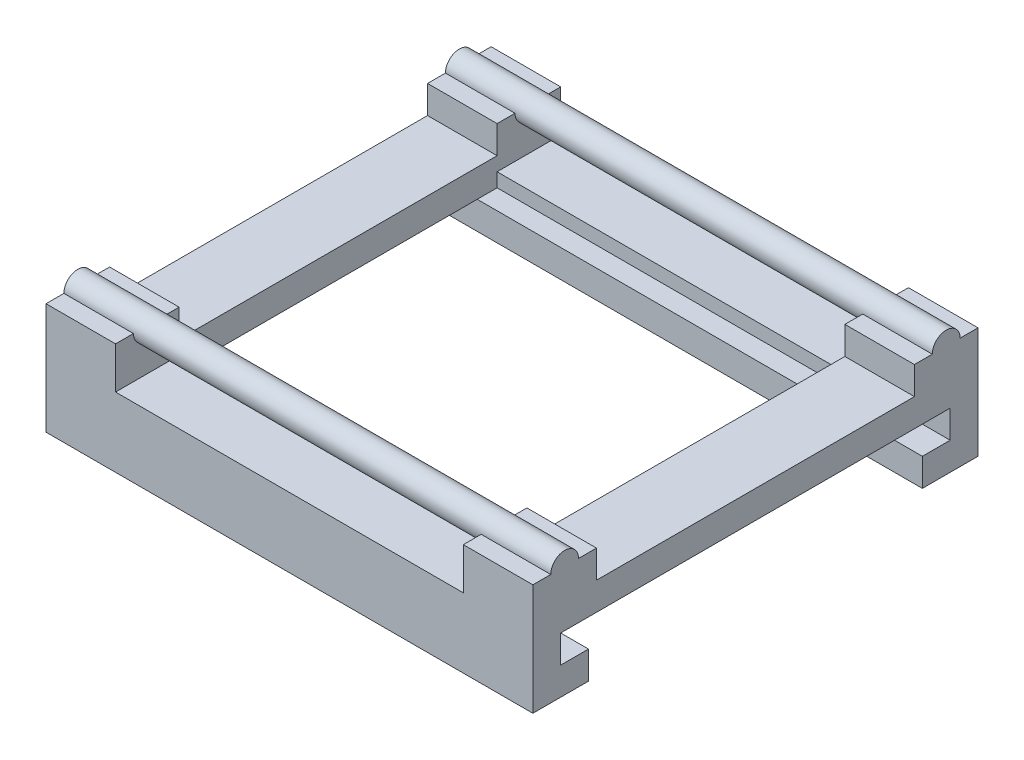
SolidWorks part; units mm, degrees
ref_plane "前视基准面" through (0, 0, 0) normal (0, 0, 1) x (1, 0, 0)
ref_plane "上视基准面" through (0, 0, 0) normal (0, 1, 0) x (1, 0, 0)
ref_plane "右视基准面" through (0, 0, 0) normal (1, 0, 0) x (0, 0, -1)
sketch "草图1" plane through (0, 0, 0) normal (0, 1, 0) x (1, 0, 0)
  line L8 (-25.1699, 20.3665) -> (9.8301, -11.6335)
  line L9 (-25.1699, 20.3665) -> (9.8301, 20.3665)
  line L10 (-25.1699, 20.3665) -> (-25.1699, -11.6335)
  line L11 (-25.1699, -11.6335) -> (9.8301, -11.6335)
  line L12 (9.8301, 20.3665) -> (9.8301, -11.6335)
  line L13 (-25.1699, -11.6335) -> (9.8301, 20.3665)
  line L15 (-20.1699, -7.0621) -> (4.8301, -7.0621)
  line L16 (-20.1699, -7.0621) -> (-20.1699, 15.7951)
  line L17 (-20.1699, 15.7951) -> (4.8301, 15.7951)
  line L18 (4.8301, -7.0621) -> (4.8301, 15.7951)
  line L19 (-20.1699, -7.0621) -> (4.8301, 15.7951) construction
  line L20 (-20.1699, 15.7951) -> (4.8301, -7.0621) construction
  point P4 (-7.6699, 4.3665)
  dimension "D1" = 32
  dimension "D2" = 35
  dimension "D3" = 25
extrude "凸台-拉伸1" add sketch "草图1" along normal blind 2 contours L13 L16 L8 L10 | L10 L9 L12 L11 region at (-22.8088, 0, -4.3665)
extrude "切除-拉伸2" cut sketch "草图1<3>" along normal blind 2 contours L16 L13 L8 | L17 L8 L13 | L8 L18 L13 | L13 L15 L8 region at (-7.6699, 0, -11.9856) region at (-16.0032, 0, -4.3665) region at (0.6634, 0, -4.3665) region at (-7.6699, 0, 3.2525)
sketch "草图1<3>" plane through (0, 0, 0) normal (0, 1, 0) x (1, 0, 0) same geometry as "草图1"
sketch "草图3" plane through (0, 0, 0) normal (0, -1, 0) x (1, 0, 0)
  line L0 (9.8301, -20.3665) -> (9.8301, 11.6335) construction
  line L1 (-25.1699, -20.3665) -> (9.8301, -20.3665)
  line L2 (-25.1699, -20.3665) -> (-25.1699, -16.3665)
  line L3 (-25.1699, -16.3665) -> (9.8301, -16.3665)
  line L4 (9.8301, -20.3665) -> (9.8301, -16.3665)
  line L6 (-25.1699, 11.6335) -> (9.8301, 11.6335)
  line L7 (-25.1699, 11.6335) -> (-25.1699, 7.6335)
  line L8 (-25.1699, 7.6335) -> (9.8301, 7.6335)
  line L9 (9.8301, 11.6335) -> (9.8301, 7.6335)
  dimension "D1" = 4
  dimension "D2" = 4
extrude "凸台-拉伸2" add sketch "草图3" along normal blind 4
sketch "草图4" plane through (0, 0, 7.6335) normal (0, 0, -1) x (-1, 0, 0)
  line L0 (25.1699, -4) -> (25.1699, 0) construction
  line L1 (-9.8301, 0) -> (25.1699, 0)
  line L2 (-9.8301, 0) -> (-9.8301, -2)
  line L3 (-9.8301, -2) -> (25.1699, -2)
  line L4 (25.1699, 0) -> (25.1699, -2)
  dimension "D1" = 2
extrude "切除-拉伸3" cut sketch "草图4" against normal blind 2
sketch "草图5" plane through (0, 0, -16.3665) normal (0, 0, 1) x (1, 0, 0)
  line L0 (-25.1699, -4) -> (-25.1699, 0) construction
  line L1 (9.8301, 0) -> (-25.1699, 0)
  line L2 (9.8301, 0) -> (9.8301, -2)
  line L3 (9.8301, -2) -> (-25.1699, -2)
  line L4 (-25.1699, 0) -> (-25.1699, -2)
extrude "切除-拉伸4" cut sketch "草图5" against normal blind 2
sketch "草图6" plane through (0, 2, 0) normal (0, 1, 0) x (1, 0, 0)
  line L1 (9.8301, -11.6335) -> (4.8301, -11.6335)
  line L2 (9.8301, -11.6335) -> (9.8301, -7.0621)
  line L3 (9.8301, -7.0621) -> (4.8301, -7.0621)
  line L4 (4.8301, -11.6335) -> (4.8301, -7.0621)
  line L5 (-25.1699, -11.6335) -> (-20.1699, -11.6335)
  line L6 (-25.1699, -11.6335) -> (-25.1699, -7.0621)
  line L7 (-25.1699, -7.0621) -> (-20.1699, -7.0621)
  line L8 (-20.1699, -11.6335) -> (-20.1699, -7.0621)
  line L9 (-25.1699, 20.3665) -> (-20.1699, 20.3665)
  line L10 (-25.1699, 20.3665) -> (-25.1699, 15.7951)
  line L11 (-25.1699, 15.7951) -> (-20.1699, 15.7951)
  line L12 (-20.1699, 20.3665) -> (-20.1699, 15.7951)
  line L13 (9.8301, 20.3665) -> (4.8301, 20.3665)
  line L14 (9.8301, 20.3665) -> (9.8301, 15.7951)
  line L15 (9.8301, 15.7951) -> (4.8301, 15.7951)
  line L16 (4.8301, 20.3665) -> (4.8301, 15.7951)
  line M19 (9.8301, -11.6335) -> (9.8301, 20.3665)
  line M20 (9.8301, 20.3665) -> (-25.1699, 20.3665)
extrude "凸台-拉伸3" add sketch "草图6" along normal blind 2 contours L16 L15 M20 M19 | L2 L1 L4 L3 | L6 L5 L8 L7 | L10 L9 L12 L11 region at (7.3301, 2, -18.0808)
sketch "草图7" plane through (0, 2, 0) normal (0, 1, 0) x (1, 0, 0)
  line L1 (-20.1699, -11.6335) -> (4.8301, -11.6335)
  line L2 (-20.1699, -11.6335) -> (-20.1699, -7.0621)
  line L3 (-20.1699, -7.0621) -> (4.8301, -7.0621)
  line L4 (4.8301, -11.6335) -> (4.8301, -7.0621)
  line L6 (4.8301, 15.7951) -> (-20.1699, 15.7951)
  line L7 (4.8301, 15.7951) -> (4.8301, 20.3665)
  line L8 (4.8301, 20.3665) -> (-20.1699, 20.3665)
  line L9 (-20.1699, 15.7951) -> (-20.1699, 20.3665)
extrude "切除-拉伸5" cut sketch "草图7" against normal blind 1
sketch "草图9" plane through (-20.1699, 0, 0) normal (1, 0, 0) x (0, 0, -1)
  line L0 (20.3665, 4) -> (15.7951, 4) construction
  line L1 (-11.6335, 4) -> (-7.0621, 4) construction
  circle A0 centre (18.0808, 4) radius 1
  circle A1 centre (-9.3478, 4) radius 1
  line M5 (20.3665, 4) -> (15.7951, 4)
extrude "凸台-拉伸4" add sketch "草图9" along normal blind 28 contours A0 M5 | A0 M5 | A1 region at (-20.1699, 4.4244, -18.0808) region at (-20.1699, 3.5756, -18.0808)
extrude "凸台-拉伸5" add sketch "草图9<3>" along normal blind 35 from surface starting at face at (-25.1699, -0.25, -4.3665)
sketch "草图9<3>" plane through (-20.1699, 0, 0) normal (1, 0, 0) x (0, 0, -1) same geometry as "草图9"
